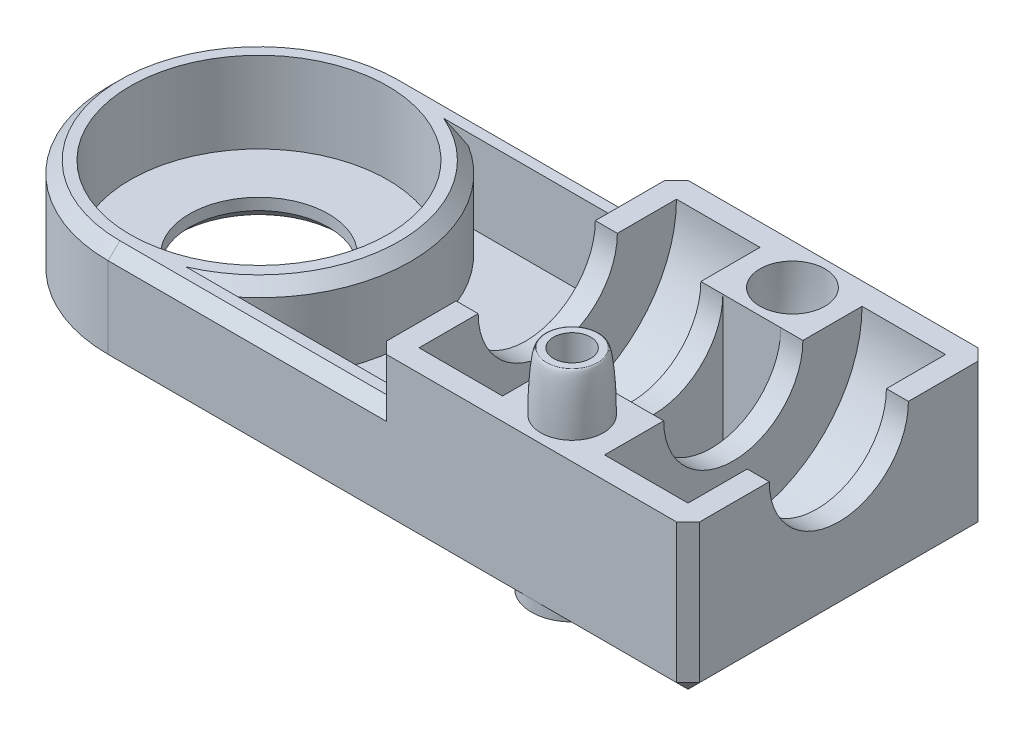
SolidWorks part; units mm, degrees
ref_plane "Front Plane" through (0, 0, 0) normal (0, 0, 1) x (1, 0, 0)
ref_plane "Top Plane" through (0, 0, 0) normal (0, 1, 0) x (1, 0, 0)
ref_plane "Right Plane" through (0, 0, 0) normal (1, 0, 0) x (0, 0, -1)
sketch "Sketch1" plane through (0, 0, 0) normal (0, 1, 0) x (1, 0, 0)
  line L1 (-13.5, -13) -> (13.5, -13)
  line L2 (-13.5, -13) -> (-13.5, 13)
  line L3 (-13.5, 13) -> (13.5, 13)
  line L4 (13.5, -13) -> (13.5, 13)
  line L5 (-13.5, -13) -> (13.5, 13) construction
  line L6 (-13.5, 13) -> (13.5, -13) construction
  point P0 (0, 0)
  dimension "D1" = 27
  dimension "D2" = 26
extrude "Boss-Extrude1" add sketch "Sketch1" along normal blind 2
sketch "Sketch2" plane through (0, 2, 0) normal (0, 1, 0) x (1, 0, 0)
  line L0 (13.5, 13) -> (-13.5, 13) construction
  line L1 (-13.5, -13) -> (-2.5, -13)
  line L2 (-13.5, -13) -> (-13.5, 13)
  line L3 (-13.5, 13) -> (-2.5, 13)
  line L4 (-2.5, -13) -> (-2.5, 13)
  dimension "D1" = 11
extrude "Boss-Extrude2" add sketch "Sketch2" along normal blind 11
ref_plane "Plane1" through (-8, 0, 0) normal (-1, 0, 0) x (0, 0, 1)
sketch "Sketch3" plane through (-8, 0, 0) normal (-1, 0, 0) x (0, 0, 1)
  line L0 (-13, 13) -> (13, 13) construction
  line L1 (11.1, 13) -> (-11.1, 13)
  arc A0 (-11.1, 13) -> (11.1, 13) centre (0, 13) ccw
  dimension "D1" = 22.2
extrude "Cut-Extrude1" cut sketch "Sketch3" against normal mid plane 7.2
sketch "Sketch4" plane through (-13.5, 0, 0) normal (-1, 0, 0) x (0, 0, 1)
  line L0 (-13, 13) -> (13, 13) construction
  line L1 (6, 13) -> (-6, 13)
  arc A0 (-6, 13) -> (6, 13) centre (0, 13) ccw
  dimension "D1" = 12
extrude "Cut-Extrude2" cut sketch "Sketch4" against normal up to surface (11 mm away) up to face at (-2.5, 7.5, 0)
ref_plane "Plane2" through (0, 0, 0) normal (1, 0, 0) x (0, 0, -1)
mirror "Mirror3" about plane through (0, 0, 0) normal (1, 0, 0) of "Cut-Extrude2", "Cut-Extrude1", "Boss-Extrude2"
sketch "Sketch13" plane through (0, 2, 0) normal (0, 1, 0) x (1, 0, 0)
  line L1 (-2.5, -13) -> (2.5, -13)
  line L2 (-2.5, -13) -> (-2.5, -6)
  line L3 (-2.5, -6) -> (2.5, -6)
  line L4 (2.5, -13) -> (2.5, -6)
  line L5 (-2.5, 6) -> (2.5, 6)
  line L6 (-2.5, 6) -> (-2.5, 13)
  line L7 (-2.5, 13) -> (2.5, 13)
  line L8 (2.5, 6) -> (2.5, 13)
extrude "Boss-Extrude6" add sketch "Sketch13" along normal up to surface (11 mm away) up to face at (-8, 13, 9.025)
sketch "Sketch14" plane through (0, 13, 0) normal (0, 1, 0) x (1, 0, 0)
  line L0 (13.5, -6) -> (13.5, -13) construction
  circle A0 centre (0, -9.5) radius 2.7
  point P7 (13.5, -9.5)
  dimension "D1" = 5.4
extrude "Boss-Extrude7" add sketch "Sketch14" along normal blind 5
sketch "Sketch15" plane through (0, 13, 0) normal (0, 1, 0) x (1, 0, 0)
  line L0 (13.5, 13) -> (13.5, 6) construction
  circle A0 centre (0, 9.5) radius 2.8
  point P5 (13.5, 9.5)
  dimension "D1" = 5.6
extrude "Cut-Extrude7" cut sketch "Sketch15" against normal blind 5 contours A0
sketch "Sketch16" plane through (0, 18, 0) normal (0, 1, 0) x (1, 0, 0)
  circle A0 centre (0, -9.5) radius 1.6
  circle A1 centre (0, 9.5) radius 1.6
  dimension "D1" = 3.2
extrude "Cut-Extrude8" cut sketch "Sketch16" against normal through all
sketch "Sketch9" plane through (0, 0, 0) normal (0, 1, 0) x (1, 0, 0)
  line L0 (-13.5, 13) -> (-13.5, -13)
  line L1 (-13.5, -13) -> (-36.5, -13)
  line L2 (-13.5, 13) -> (-36.5, 13)
  line L3 (13.5, -6) -> (13.5, 6) construction
  arc A0 (-36.5, 13) -> (-36.5, -13) centre (-36.5, 0) ccw
  dimension "D1" = 50
extrude "Boss-Extrude5" add sketch "Sketch9" along normal blind 9 contours L1 A0 L2 L0
sketch "Sketch10" plane through (0, 9, 0) normal (0, 1, 0) x (1, 0, 0)
  circle A0 centre (-36.5, 0) radius 11.1
  dimension "D1" = 22.2
extrude "Cut-Extrude4" cut sketch "Sketch10" against normal blind 7
sketch "Sketch11" plane through (0, 2, 0) normal (0, 1, 0) x (1, 0, 0)
  circle A0 centre (-36.5, 0) radius 6
  dimension "D1" = 12
extrude "Cut-Extrude5" cut sketch "Sketch11" against normal through all
sketch "Sketch12" plane through (0, 9, 0) normal (0, 1, 0) x (1, 0, 0)
  line L0 (-29.543, -11.1) -> (-13.5, -11.1)
  line L1 (-13.5, -6) -> (-13.5, -13) construction
  line L2 (-13.5, -11.1) -> (-13.5, 11.1)
  line L3 (-13.5, 13) -> (-13.5, 4.4721) construction
  line L4 (-13.5, 11.1) -> (-29.543, 11.1)
  arc A0 (-29.543, 11.1) -> (-29.543, -11.1) centre (-36.5, 0) cw
  circle A1 centre (-36.5, 0) radius 11.1 construction
  point P4 (-13.5, 0)
  dimension "D1" = 2
extrude "Cut-Extrude6" cut sketch "Sketch12" against normal blind 7
chamfer "Chamfer4" distance 1 angle 45 13 edges at (-11.5, 0, -13) (-49.5, 0, 0) (-11.5, 0, 13) (-36.5, 0, 6) (-23.4, 9, 0) (-25, 9, -13) (-25, 9, 13) (-49.5, 9, 0) (-13.5, 11, -13) (-13.5, 11, 13) (13.5, 6.5, -13) (13.5, 0, 0) (13.5, 6.5, 13)
sketch "Sketch17" plane through (0, 0, 0) normal (0, -1, 0) x (1, 0, 0)
  line L0 (12.5, -13) -> (-36.5, -13) construction
  line L1 (-36.5, 13) -> (12.5, 13) construction
  circle A0 centre (0, -9.5) radius 3.5
  circle A1 centre (0, 9.5) radius 3.5
  circle A2 centre (0, -9.5) radius 1.6
  circle A3 centre (0, 9.5) radius 1.6
extrude "Boss-Extrude9" add sketch "Sketch17" against normal up to vertex (1 mm away) up to point (12.5, 1, 13)
fillet "Fillet1" radius 5 2 edges at (0, 8, -6.7) (0, 18, 12.2) second distance 0.5 first distance on face at (0, 8, -6.7) first distance on face at (0, 18, 12.2)
equation "\"bearing_depth\"= 7"
equation "\"D1@Sketch1\"=\"bearing_depth\"*2+8+5"
equation "\"bearing_od\"= 22"
equation "\"D2@Sketch1\"=\"bearing_od\"+4"
equation "\"D1@Sketch2\"=\"bearing_depth\"+4"
equation "\"D1@Boss-Extrude2\"=\"bearing_od\"/2"
equation "\"print_tolerance\"=0.1"
equation "\"D1@Sketch3\"=\"print_tolerance\"*2+\"bearing_od\""
equation "\"D1@Cut-Extrude1\"=\"bearing_depth\"+2*\"print_tolerance\""
equation "\"bearing_axel\"= 12"
equation "\"D1@Sketch4\"=\"bearing_axel\""
equation "\"length\"=50"
equation "\"D1@Sketch9\"= \"length\""
equation "\"D1@Boss-Extrude5\"=\"bearing_depth\"+2"
equation "\"D1@Sketch10\"=\"bearing_od\"+2*\"print_tolerance\""
equation "\"D1@Cut-Extrude4\"=\"bearing_depth\""
equation "\"D1@Sketch11\"=\"bearing_axel\""
equation "\"D1@Cut-Extrude6\"=\"bearing_depth\""
equation "\"D1@Sketch14\"=5.5-\"print_tolerance\""
equation "\"D1@Boss-Extrude7\"=\"bearing_depth\""
equation "\"D1@Sketch15\"=5.5+\"print_tolerance\""
equation "\"D1@Cut-Extrude7\"=\"bearing_depth\""
equation "\"D1@Sketch16\"=3+2*\"print_tolerance\""
